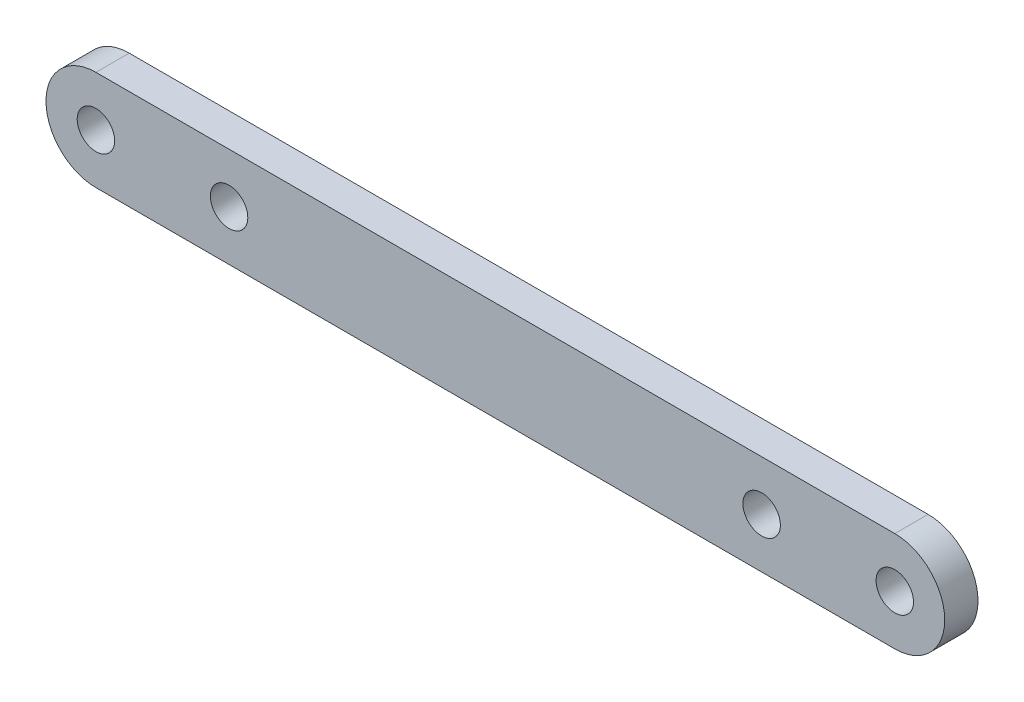
SolidWorks part; units mm, degrees
ref_plane "Front Plane" through (0, 0, 0) normal (0, 0, 1) x (1, 0, 0)
ref_plane "Top Plane" through (0, 0, 0) normal (0, 1, 0) x (1, 0, 0)
ref_plane "Right Plane" through (0, 0, 0) normal (1, 0, 0) x (0, 0, -1)
sketch "Sketch1" plane through (0, 0, 0) normal (0, 0, 1) x (1, 0, 0)
  line L0 (0, 0) -> (-76.2, 0) construction
  line L1 (0, -4.7625) -> (-76.2, -4.7625)
  line L2 (0, 4.7625) -> (-76.2, 4.7625)
  arc A0 (0, -4.7625) -> (0, 4.7625) centre (0, 0) ccw
  arc A1 (-76.2, 4.7625) -> (-76.2, -4.7625) centre (-76.2, 0) ccw
  point P3 (-38.1, 0)
  dimension "D1" = 9.525
  dimension "D2" = 76.2
extrude "Boss-Extrude1" add sketch "Sketch1" along normal blind 3.175
hole_wizard "9/64 (0.14063) Diameter Hole1" positions "Sketch3" profile "Sketch2" hole size "9/64" standard "ANSI Inch" end condition through all
sketch "Sketch3" plane through (0, 0, 3.175) normal (0, 0, 1) x (1, 0, 0)
  point P0 (0, 0)
  point P3 (-76.2, 0)
sketch "Sketch2" plane through (0, 0, 3.175) normal (1, 0, 0) x (0, -1, 0)
  line L0 (0, 0) -> (0, 3.175)
  line L1 (0, 3.175) -> (1.786, 3.175)
  line L2 (1.786, 3.175) -> (1.786, 0)
  line L5 (1.786, 0) -> (0, 0)
  line L11 (0, -6.35) -> (0, 107.95) construction
  dimension "Thru Hole Dia." = 3.572
  dimension "Thru Hole Depth" = 3.175
hole_wizard "9/64 (0.14063) Diameter Hole2" positions "Sketch5" profile "Sketch4" hole size "9/64" standard "ANSI Inch" end condition through all
sketch "Sketch5" plane through (0, 0, 3.175) normal (0, 0, 1) x (1, 0, 0)
  line L0 (-38.1, 4.7625) -> (-38.1, -4.7625) construction
  line L1 (0, 4.7625) -> (-76.2, 4.7625) construction
  line L2 (-76.2, -4.7625) -> (0, -4.7625) construction
  point P0 (-12.7, 0)
  point P13 (-63.5, 0)
  dimension "D1" = 12.7
sketch "Sketch4" plane through (-12.7, 0, 3.175) normal (1, 0, 0) x (0, -1, 0)
  line L0 (0, 0) -> (0, 3.175)
  line L1 (0, 3.175) -> (1.786, 3.175)
  line L2 (1.786, 3.175) -> (1.786, 0)
  line L5 (1.786, 0) -> (0, 0)
  line L11 (0, -6.35) -> (0, 107.95) construction
  dimension "Thru Hole Dia." = 3.572
  dimension "Thru Hole Depth" = 3.175
